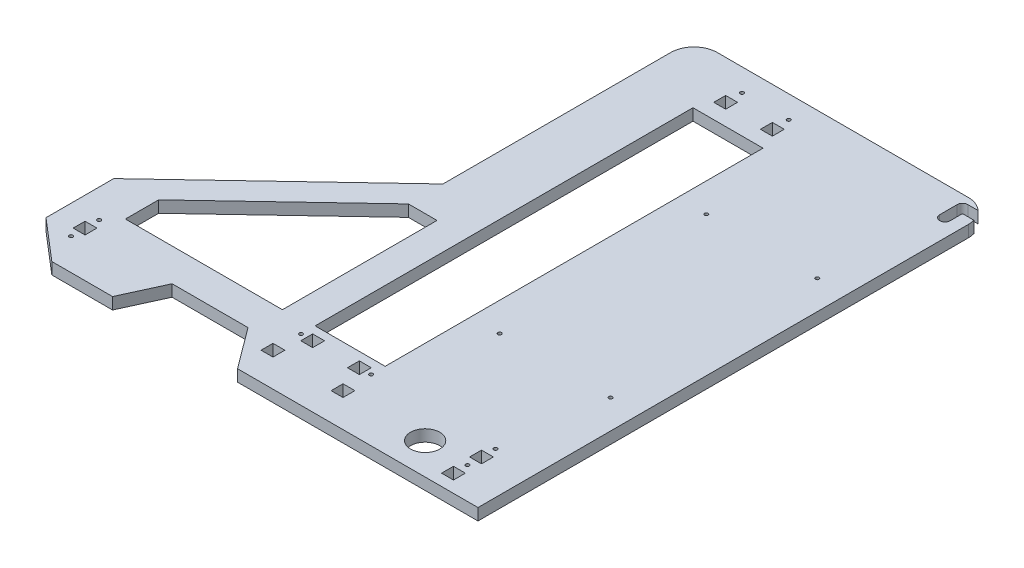
SolidWorks part; units mm, degrees
ref_plane "Front Plane" through (0, 0, 0) normal (0, 0, 1) x (1, 0, 0)
ref_plane "Top Plane" through (0, 0, 0) normal (0, 1, 0) x (1, 0, 0)
ref_plane "Right Plane" through (0, 0, 0) normal (1, 0, 0) x (0, 0, -1)
sketch "Sketch1" plane through (0, 0, 0) normal (0, 1, 0) x (1, 0, 0)
  line L0 (0, 0) -> (-235, 0)
  line L1 (-235, 0) -> (-235, -215)
  line L2 (-235, -215) -> (-380, -352)
  line L3 (-380, -352) -> (-380, -410)
  line L4 (-380, -410) -> (-345, -440)
  line L5 (-345, -440) -> (-293, -440)
  line L6 (-293, -440) -> (-277, -405)
  line L7 (-277, -405) -> (-212, -405)
  line L8 (-212, -405) -> (-185.9255, -440)
  line L9 (-185.9255, -440) -> (0, -440)
  line L10 (0, 0) -> (0, -440)
  line L12 (-293, -440) -> (-185.9255, -440) construction
  dimension "D3" = 235
  dimension "D5" = 58
  dimension "D13" = 190
  dimension "D7" = 35
  dimension "D2" = 126.686
  dimension "D11" = 65
  dimension "D15" = 52
  dimension "D12" = 30
  dimension "D10" = 35
  dimension "D14" = 16
  dimension "D6" = 380
  dimension "D4" = 440
extrude "Boss-Extrude1" add sketch "Sketch1" along normal blind 10
sketch "Sketch16" plane through (0, 10, 0) normal (0, 1, 0) x (1, 0, 0)
  line L0 (0, -440) -> (20, -440)
  line L1 (20, -440) -> (20, 0)
  line L2 (20, 0) -> (0, 0)
  line L3 (0, 0) -> (0, -440)
  dimension "D1" = 20
  dimension "D2" = 90
extrude "Boss-Extrude2" add sketch "Sketch16" against normal through all
sketch "Sketch2" plane through (0, 10, 0) normal (0, 1, 0) x (1, 0, 0)
  line L0 (-235, -215) -> (-235, -405) construction
  line L1 (-277, -405) -> (-212, -405) construction
  line L2 (-345, -440) -> (-345, -318.931) construction
  line L3 (-235, -215) -> (-380, -352) construction
  line L4 (-345, -348.5097) -> (-235, -244.5787)
  line L5 (-235, -244.5787) -> (-210.5, -244.5787)
  line L6 (-210.5, -244.5787) -> (-210.5, -377)
  line L7 (-210.5, -377) -> (-345, -377)
  line L8 (-345, -377) -> (-345, -348.5097)
  line L9 (0, -440) -> (0, 0) construction
  line L10 (-184.5, -375) -> (-124.5, -375)
  line L11 (-184.5, -375) -> (-184.5, -51.35)
  line L12 (-184.5, -51.35) -> (-124.5, -51.35)
  line L13 (-124.5, -375) -> (-124.5, -51.35)
  line L14 (-124.5, -387.1) -> (-184.5, -387.1) construction
  line L15 (-16, -440) -> (-16, 0) construction
  line L16 (20, 0) -> (-235, 0) construction
  line L17 (-355.55, -430.9571) -> (-355.55, -328.899) construction
  line L18 (-21.1, -430.1) -> (-10.9, -430.1)
  line L19 (-21.1, -430.1) -> (-21.1, -419.9)
  line L20 (-21.1, -419.9) -> (-10.9, -419.9)
  line L21 (-10.9, -430.1) -> (-10.9, -419.9)
  line L22 (-21.1, -430.1) -> (-10.9, -419.9) construction
  line L23 (-21.1, -419.9) -> (-10.9, -430.1) construction
  line L24 (-21.1, -406.1) -> (-10.9, -406.1)
  line L25 (-21.1, -406.1) -> (-21.1, -395.9)
  line L26 (-21.1, -395.9) -> (-10.9, -395.9)
  line L27 (-10.9, -406.1) -> (-10.9, -395.9)
  line L28 (-21.1, -406.1) -> (-10.9, -395.9) construction
  line L29 (-21.1, -395.9) -> (-10.9, -406.1) construction
  line L30 (-380, -410) -> (-345, -440) construction
  line L32 (-350.45, -395.9) -> (-360.65, -395.9)
  line L33 (-350.45, -395.9) -> (-350.45, -406.1)
  line L34 (-350.45, -406.1) -> (-360.65, -406.1)
  line L35 (-360.65, -395.9) -> (-360.65, -406.1)
  line L36 (-350.45, -395.9) -> (-360.65, -406.1) construction
  line L37 (-350.45, -406.1) -> (-360.65, -395.9) construction
  line L38 (-185.9255, -440) -> (20, -440) construction
  line L39 (-185.9255, -440) -> (20, -440) construction
  line L40 (-173.924, -33.35) -> (-113.924, -33.35) construction
  line L41 (-154.5, -51.35) -> (-154.5, -33.35) construction
  line L42 (-179.6, -28.25) -> (-169.4, -28.25)
  line L43 (-179.6, -28.25) -> (-179.6, -38.45)
  line L44 (-179.6, -38.45) -> (-169.4, -38.45)
  line L45 (-169.4, -28.25) -> (-169.4, -38.45)
  line L46 (-179.6, -28.25) -> (-169.4, -38.45) construction
  line L47 (-179.6, -38.45) -> (-169.4, -28.25) construction
  line L48 (-129.4, -38.45) -> (-139.6, -28.25) construction
  line L49 (-129.4, -28.25) -> (-139.6, -38.45) construction
  line L50 (-139.6, -28.25) -> (-139.6, -38.45)
  line L51 (-129.4, -38.45) -> (-139.6, -38.45)
  line L52 (-129.4, -28.25) -> (-129.4, -38.45)
  line L53 (-129.4, -28.25) -> (-139.6, -28.25)
  line L54 (-174.5, -33.35) -> (-174.5, -19.35) construction
  line L55 (-134.5, -33.35) -> (-134.5, -19.35) construction
  line L56 (-154.5, -375) -> (-154.5, -440) construction
  line L57 (-174.5, -387.1) -> (-134.5, -387.1) construction
  line L58 (-129.4, -392.2) -> (-139.6, -382) construction
  line L59 (-179.6, -382) -> (-169.4, -382)
  line L60 (-179.6, -382) -> (-179.6, -392.2)
  line L61 (-179.6, -392.2) -> (-169.4, -392.2)
  line L62 (-169.4, -382) -> (-169.4, -392.2)
  line L63 (-179.6, -382) -> (-169.4, -392.2) construction
  line L64 (-179.6, -392.2) -> (-169.4, -382) construction
  line L65 (-129.4, -382) -> (-139.6, -392.2) construction
  line L66 (-139.6, -382) -> (-139.6, -392.2)
  line L67 (-129.4, -392.2) -> (-139.6, -392.2)
  line L68 (-129.4, -382) -> (-129.4, -392.2)
  line L69 (-129.4, -382) -> (-139.6, -382)
  line L70 (-119.4, -416.2) -> (-129.6, -406) construction
  line L71 (-189.6, -406) -> (-179.4, -406)
  line L72 (-189.6, -406) -> (-189.6, -416.2)
  line L73 (-189.6, -416.2) -> (-179.4, -416.2)
  line L74 (-179.4, -406) -> (-179.4, -416.2)
  line L75 (-189.6, -406) -> (-179.4, -416.2) construction
  line L76 (-189.6, -416.2) -> (-179.4, -406) construction
  line L77 (-119.4, -406) -> (-129.6, -416.2) construction
  line L78 (-129.6, -406) -> (-129.6, -416.2)
  line L79 (-119.4, -416.2) -> (-129.6, -416.2)
  line L80 (-119.4, -406) -> (-119.4, -416.2)
  line L81 (-119.4, -406) -> (-129.6, -406)
  line L82 (-360.65, -395.9) -> (-10.9, -395.9) construction
  circle A0 centre (-16, -413) radius 1.55
  circle A1 centre (-16, -389) radius 1.55
  circle A2 centre (-355.55, -413) radius 1.55
  circle A3 centre (-355.55, -389) radius 1.55
  circle A4 centre (-174.5, -19.35) radius 1.55
  circle A5 centre (-134.5, -19.35) radius 1.55
  circle A6 centre (-124.5, -387.1) radius 1.55
  circle A7 centre (-184.5, -387.1) radius 1.55
  point P25 (-16, -425)
  point P30 (-16, -401)
  point P44 (-355.55, -401)
  point P61 (-174.5, -33.35)
  point P72 (-134.5, -33.35)
  point P85 (-174.5, -387.1)
  point P94 (-134.5, -387.1)
  point P95 (-184.5, -411.1)
  point P104 (-124.5, -411.1)
  point P105 (-154.5, -387.1)
  dimension "D13" = 3.1
  dimension "D14" = 3.1
  dimension "D23" = 3.1
  dimension "D24" = 3.1
  dimension "D31" = 3.1
  dimension "D37" = 3.1
  dimension "D1" = 21.5
  dimension "D2" = 28
  dimension "D3" = 24.5
  dimension "D4" = 60
  dimension "D7" = 26
  dimension "D8" = 10.2
  dimension "D9" = 10.2
  dimension "D10" = 10.2
  dimension "D11" = 10.2
  dimension "D12" = 24
  dimension "D15" = 24
  dimension "D19" = 10.2
  dimension "D20" = 10.2
  dimension "D26" = 12
  dimension "D27" = 10.2
  dimension "D28" = 10.2
  dimension "D33" = 10.2
  dimension "D38" = 10.2
  dimension "D39" = 10.2
  dimension "D41" = 24
  dimension "D34" = 30
  dimension "D36" = 12.1
  dimension "D30" = 18
  dimension "D29" = 40
  dimension "D17" = 15
  dimension "D32" = 14
  dimension "D35" = 20
  dimension "D16" = 12
  dimension "D21" = 90
  dimension "D25" = 24
  dimension "D5" = 353.75
  dimension "D22" = 349.75
  dimension "D40" = 30
  dimension "D6" = 65
  dimension "D42" = 0
  dimension "D43" = 0
  dimension "D18" = 16
extrude "Cut-Extrude1" cut sketch "Sketch2" against normal through all
fillet "Fillet1" radius 20 2 edges at (-235, 5, 0) (20, 5, 0)
sketch "Sketch11" plane through (0, 10, 0) normal (0, 1, 0) x (1, 0, 0)
  line L0 (-124.5, -213.175) -> (20, -213.175) construction
  line L1 (20, -440) -> (20, -20) construction
  line L3 (-52.25, -213.175) -> (-52.25, -440) construction
  line L6 (-124.5, -375) -> (-124.5, -51.35) construction
  line L8 (-185.9255, -440) -> (20, -440) construction
  circle A0 centre (-52.25, -413) radius 12.5
  circle A1 centre (-16, -413) radius 1.55 construction
  dimension "D1" = 25
  dimension "D2" = 0
  dimension "D3" = 0
extrude "WiringHole" cut sketch "Sketch11" against normal through all
sketch "Sketch9" plane through (0, 10, 0) normal (0, 1, 0) x (1, 0, 0)
  line L0 (-52.25, -400.5) -> (-52.25, 0) construction
  line L1 (0, 0) -> (-215, 0) construction
  line L2 (-124.5, -213.175) -> (20, -213.175) construction
  line L3 (-124.5, -375) -> (-124.5, -51.35) construction
  line L4 (-4.75, -124.675) -> (-4.75, -301.675) construction
  line L6 (-99.75, -124.675) -> (-4.75, -124.675) construction
  line L7 (-4.75, -301.675) -> (-99.75, -301.675) construction
  line L8 (-99.75, -301.675) -> (-99.75, -124.675) construction
  line L9 (20, -440) -> (20, -20) construction
  circle A0 centre (-52.25, -413) radius 12.5 construction
  circle A1 centre (-99.75, -124.675) radius 1.55
  circle A2 centre (-4.75, -124.675) radius 1.55
  circle A3 centre (-4.75, -301.675) radius 1.55
  circle A4 centre (-99.75, -301.675) radius 1.55
  dimension "D3" = 3.1
  dimension "D4" = 3.1
  dimension "D1" = 95
  dimension "D2" = 177
  dimension "D5" = 47.5
extrude "MountingHoles-PSU" cut sketch "Sketch9" against normal through all
sketch "Sketch10" [suppressed] plane through (0, 10, 0) normal (0, 1, 0) x (1, 0, 0)
  line L0 (-124.5, -213.175) -> (20, -213.175) construction
  line L1 (20, -440) -> (20, -20) construction
  line L2 (-64.75, -228.175) -> (-39.75, -228.175) construction
  line L3 (-52.25, -213.175) -> (-52.25, 0) construction
  line L7 (-124.5, -375) -> (-124.5, -51.35) construction
  line L8 (-64.75, -278.175) -> (-39.75, -278.175)
  line L9 (-64.75, -278.175) -> (-64.75, -178.175)
  line L10 (-64.75, -178.175) -> (-39.75, -178.175)
  line L11 (-39.75, -278.175) -> (-39.75, -178.175)
  line L12 (-64.75, -278.175) -> (-39.75, -178.175) construction
  line L13 (-64.75, -178.175) -> (-39.75, -278.175) construction
  line L15 (0, 0) -> (-215, 0) construction
  line L17 (-52.25, -213.175) -> (-52.25, -440) construction
  line L18 (-185.9255, -440) -> (20, -440) construction
  line L19 (-64.75, -213.175) -> (-39.75, -213.175) construction
  line L20 (-52.25, -278.175) -> (-52.25, -178.175) construction
  dimension "D1" = 25
  dimension "D2" = 100
  dimension "D3" = 0
  dimension "D4" = 0
  dimension "D5" = 0
  dimension "D6" = 15
extrude "WiringSlot" [suppressed] cut sketch "Sketch10" against normal through all
sketch "CenterLines" [suppressed] plane through (0, 10, 0) normal (0, 1, 0) x (1, 0, 0)
  line L0 (-52.25, -278.175) -> (-52.25, -178.175) construction
  line L1 (-64.75, -278.175) -> (-39.75, -278.175) construction
  line L2 (-39.75, -178.175) -> (-64.75, -178.175) construction
  line L3 (-64.75, -228.175) -> (-39.75, -228.175) construction
  line L4 (-64.75, -178.175) -> (-64.75, -278.175) construction
  line L5 (-39.75, -278.175) -> (-39.75, -178.175) construction
ref_plane "Plane1" [suppressed] through (-52.25, 0, 0) normal (1, 0, 0) x (0, 0, -1)
sketch "Sketch6" [suppressed] plane through (0, 10, 0) normal (0, 1, 0) x (1, 0, 0)
  line L0 (-52.25, -278.175) -> (-52.25, -178.175) construction
  line L1 (-76.35, -237.025) -> (-28.15, -237.025) construction
  line L2 (-28.15, -192.575) -> (-28.15, -275.075) construction
  line L3 (-64.75, -278.175) -> (-39.75, -278.175) construction
  line L4 (-64.75, -245.875) -> (-39.75, -245.875) construction
  line L5 (-39.75, -178.175) -> (-64.75, -178.175) construction
  line L6 (-28.15, -192.575) -> (-28.15, -199.575) construction
  line L7 (-26.6, -192.575) -> (-26.6, -199.575)
  line L8 (-29.7, -192.575) -> (-29.7, -199.575)
  line L9 (-64.75, -228.175) -> (-39.75, -228.175) construction
  line L10 (-64.75, -178.175) -> (-64.75, -278.175) construction
  line L11 (-39.75, -278.175) -> (-39.75, -178.175) construction
  line L12 (-28.15, -282.075) -> (-28.15, -275.075) construction
  line L13 (-29.7, -282.075) -> (-29.7, -275.075)
  line L14 (-76.35, -274.475) -> (-76.35, -199.575) construction
  line L15 (-28.15, -282.075) -> (-28.15, -199.575) construction
  line L16 (-26.6, -282.075) -> (-26.6, -275.075)
  arc A2 (-26.6, -192.575) -> (-29.7, -192.575) centre (-28.15, -192.575) ccw
  arc A3 (-29.7, -199.575) -> (-26.6, -199.575) centre (-28.15, -199.575) ccw
  circle A4 centre (-76.35, -274.475) radius 1.55
  circle A6 centre (-76.35, -199.575) radius 1.55
  arc A8 (-29.7, -282.075) -> (-26.6, -282.075) centre (-28.15, -282.075) ccw
  arc A9 (-26.6, -275.075) -> (-29.7, -275.075) centre (-28.15, -275.075) ccw
  point P20 (-28.15, -196.075)
  point P25 (-28.15, -278.575)
  dimension "D8" = 3.1
  dimension "D12" = 3.1
  dimension "D4" = 1.55
  dimension "D5" = 1.55
  dimension "D11" = 82.5
  dimension "D14" = 74.9
  dimension "D2" = 24.1
  dimension "D3" = 48.2
  dimension "D6" = 8.85
  dimension "D9" = 7
  dimension "D10" = 7
extrude "MountingHoles-RAMPS" [suppressed] cut sketch "Sketch6" against normal through all
mirror "Mirror1" [suppressed] about plane through (-52.25, 0, 0) normal (1, 0, 0)
sketch "Sketch5" [suppressed] plane through (0, 10, 0) normal (0, 1, 0) x (1, 0, 0)
  line L0 (-39.75, -228.175) -> (-64.75, -228.175) construction
  line L3 (-39.75, -278.175) -> (-39.75, -178.175) construction
  line L5 (-64.75, -178.175) -> (-64.75, -278.175) construction
  line L7 (-31.25, -127.675) -> (-73.25, -127.675) construction
  line L8 (-31.25, -328.675) -> (-73.25, -328.675) construction
  line L9 (-52.25, -228.175) -> (-52.25, -127.675) construction
  line L10 (-52.25, -228.175) -> (-52.25, -328.675) construction
  circle A0 centre (-73.25, -127.675) radius 1.55
  circle A1 centre (-31.25, -127.675) radius 1.55
  circle A2 centre (-31.25, -328.675) radius 1.55
  circle A3 centre (-73.25, -328.675) radius 1.55
  point P17 (-52.25, -127.675)
  point P22 (-52.25, -328.675)
  dimension "D2" = 3.1
  dimension "D5" = 3.1
  dimension "D6" = 3.1
  dimension "D7" = 3.1
  dimension "D3" = 201
  dimension "D4" = 100.5
  dimension "D8" = 21
  dimension "D9" = 21
  dimension "D10" = 100.5
extrude "MountingHoles-Melzi" [suppressed] cut sketch "Sketch5" against normal through all
sketch "Sketch13" [suppressed] plane through (0, 0, 0) normal (0, -1, 0) x (-1, 0, 0)
  line L0 (64.75, -213.175) -> (124.5, -213.175) construction
  line L1 (124.5, -375) -> (124.5, -51.35) construction
  line L2 (101.46, -262.69) -> (101.46, -163.66) construction
  line L3 (52.25, -278.175) -> (52.25, -178.175) construction
  line L4 (64.75, -178.175) -> (64.75, -278.175) construction
  line L6 (101.46, -262.69) -> (3.56, -262.69) construction
  circle A0 centre (101.46, -163.66) radius 1.55
  circle A1 centre (101.46, -262.69) radius 1.55
  circle A2 centre (8.62, -170.14) radius 1.55
  circle A3 centre (3.56, -262.69) radius 1.55
  point P11 (101.46, -213.175)
  dimension "D8" = 3.1
  dimension "D6" = 3.1
  dimension "D1" = 3.1
  dimension "D2" = 49.515
  dimension "D3" = 49.21
  dimension "D4" = 6.48
  dimension "D5" = 92.84
  dimension "D7" = 97.9
extrude "Mountingholes-Smoothieboard" [suppressed] cut sketch "Sketch13" against normal through all
mirror "Flipped" [suppressed] about plane through (-52.25, 0, 0) normal (1, 0, 0)
sketch "Sketch21" [suppressed] plane through (0, 10, 0) normal (0, 1, 0) x (1, 0, 0)
  line L0 (-52.25, -178.175) -> (-52.25, 0) construction
  line L1 (-39.75, -178.175) -> (-64.75, -178.175) construction
  line L2 (0, 0) -> (-215, 0) construction
  line L3 (-52.25, -62.675) -> (-23.3697, -62.675) construction
  circle A0 centre (-27.75, -33.675) radius 1.55
  circle A1 centre (-76.75, -33.675) radius 1.55
  circle A2 centre (-76.75, -91.675) radius 1.55
  circle A3 centre (-27.75, -91.675) radius 1.55
  circle A4 centre (-31.25, -127.675) radius 1.55 construction
  dimension "D1" = 3.1
  dimension "D2" = 24.5
  dimension "D3" = 29
  dimension "D4" = 65
extrude "Pi" [suppressed] cut sketch "Sketch21" against normal through all
sketch "Sketch17" plane through (0, 10, 0) normal (0, 1, 0) x (1, 0, 0)
  line L0 (0, 0) -> (20, 0) construction
  line L1 (20, -23.6361) -> (20, 0) construction
  line L2 (20, -440) -> (20, -20) construction
  line L3 (20, -10) -> (5, -10) construction
  line L4 (20, -14.5) -> (5, -14.5)
  line L5 (20, -5.5) -> (5, -5.5)
  arc A0 (20, -14.5) -> (20, -5.5) centre (20, -10) ccw
  arc A1 (5, -5.5) -> (5, -14.5) centre (5, -10) ccw
  point P8 (12.5, -10)
  dimension "D1" = 9
  dimension "D2" = 15
  dimension "D3" = 10
extrude "Cut-Extrude3" cut sketch "Sketch17" against normal through all
sketch "Sketch18" plane through (0, 10, 0) normal (0, 1, 0) x (1, 0, 0)
  line L0 (5, -5.5) -> (5, -14.5) construction
  line L1 (0.5, -10) -> (5, -10) construction
  line L2 (5, -10) -> (5, -25) construction
  line L3 (9.5, -10) -> (9.5, -25)
  line L4 (0.5, -10) -> (0.5, -25)
  arc A0 (5, -5.5) -> (5, -14.5) centre (5, -10) ccw construction
  arc A1 (9.5, -10) -> (0.5, -10) centre (5, -10) ccw
  arc A2 (0.5, -25) -> (9.5, -25) centre (5, -25) ccw
  point P10 (5, -17.5)
  dimension "D1" = 9
  dimension "D2" = 0
  dimension "D3" = 15
extrude "Cut-Extrude4" cut sketch "Sketch18" against normal through all
sketch "Sketch19" plane through (0, 10, 0) normal (0, 1, 0) x (1, 0, 0)
  line L0 (-5, -25) -> (15, -25) construction
  line L1 (5, -25) -> (5, -5.5) construction
  circle A0 centre (15, -25) radius 1.55
  arc A1 (5, -5.5) -> (0.5, -10) centre (5, -10) ccw construction
  circle A2 centre (-5, -25) radius 1.55
  dimension "D2" = 3.1
extrude "Cut-Extrude5" [suppressed] cut sketch "Sketch19" against normal through all
equation "\"Y-ROD-SPACING\"=75"
equation "\"Y-BED-OFFSET\"=2"
equation "\"Y-BED-ROD-INSET\"=3.5"
equation "\"T-SLOT-NUT-FILLET-RADIUS\"=0.25"
equation "\"T-SLOT-SCREW-SHAFT-RADIUS\"=1.75"
equation "\"T-SLOT-SCREW-SHAFT-CUTOUT-LENGTH\"=10.5"
equation "\"T-SLOT-NUT-DEPTH\"=4.2"
equation "\"T-SLOT-NUT-WIDTH\"=3"
equation "\"T-SLOT-NUT-END-DISTANCE\"=8"
equation "\"ACRYLIC-TAB-CUTOUT-SIZE\"=\"ACRYLIC-THICKNESS\"+\"ACRYLIC-TAB-TOLERANCE\"*2"
equation "\"ACRYLIC-TAB-WIDTH\"=\"ACRYLIC-THICKNESS\""
equation "\"ACRYLIC-M3-HOLE\"=3.1"
equation "\"SMOOTHROD-CAP-SCREW-DISTANCE\"=20"
equation "\"FRAME-WIDTH-INNER\"=370"
equation "\"D24@Sketch2\"=\"ACRYLIC-M3-HOLE\""
equation "\"D23@Sketch2\"=\"ACRYLIC-M3-HOLE\""
equation "\"D19@Sketch2\"=\"ACRYLIC-THICKNESS\"+\"ACRYLIC-TAB-TOLERANCE\"*2"
equation "\"D20@Sketch2\"=\"ACRYLIC-TAB-WIDTH\"+\"ACRYLIC-TAB-TOLERANCE\"*2"
equation "\"D37@Sketch2\"=\"ACRYLIC-M3-HOLE\""
equation "\"D33@Sketch2\"=\"ACRYLIC-TAB-CUTOUT-SIZE\""
equation "\"D38@Sketch2\"=\"ACRYLIC-TAB-CUTOUT-SIZE\""
equation "\"D39@Sketch2\"=\"ACRYLIC-TAB-CUTOUT-SIZE\""
equation "\"D13@Sketch2\"=\"ACRYLIC-M3-HOLE\""
equation "\"D14@Sketch2\"=\"ACRYLIC-M3-HOLE\""
equation "\"D8@Sketch2\"=\"ACRYLIC-TAB-CUTOUT-SIZE\""
equation "\"D9@Sketch2\"=\"ACRYLIC-TAB-CUTOUT-SIZE\""
equation "\"D10@Sketch2\"=\"ACRYLIC-TAB-CUTOUT-SIZE\""
equation "\"D11@Sketch2\"=\"ACRYLIC-TAB-CUTOUT-SIZE\""
equation "\"D31@Sketch2\"=\"ACRYLIC-M3-HOLE\""
equation "\"D27@Sketch2\"=\"ACRYLIC-THICKNESS\"+\"ACRYLIC-TAB-TOLERANCE\"*2"
equation "\"D28@Sketch2\"=\"ACRYLIC-TAB-WIDTH\"+\"ACRYLIC-TAB-TOLERANCE\"*2"
equation "\"NEMA17-HOLE-SPACING\"=31"
equation "\"NEMA17-CENTRAL-CUTOUT\"=22.5"
equation "\"Z-BRACKET-REACH\"=55"
equation "\"TOP-BRACKET-SPACING\"=40"
equation "\"D29@Sketch2\"=\"TOP-BRACKET-SPACING\""
equation "\"ACRYLIC-THICKNESS\"=10"
equation "\"SMOOTHROD-Z-LENGTH\"=350"
equation "\"D5@Sketch2\"=\"SMOOTHROD-Z-LENGTH\"-\"SMOOTHROD-TIGHTENING-HEADROOM\"+4"
equation "\"SMOOTHROD-X-LENGTH\"=350"
equation "\"SMOOTHROD-Y-LENGTH\"=350"
equation "\"D22@Sketch2\"=\"SMOOTHROD-Y-LENGTH\"-\"SMOOTHROD-TIGHTENING-HEADROOM\""
equation "\"SMOOTHROD-TIGHTENING-HEADROOM\"=.25"
equation "\"X-ROD-SPACING\"=45"
equation "\"Z-ROD-SPACING\"=17.5"
equation "\"LEADSCREW-Z-LENGTH\"=300"
equation "\"SCREW-HEAD-RADIUS\"=6"
equation "\"PRINTED-X-SMOOTHROD-DIAMETER\"=8.2"
equation "\"PRINTED-X-SMOOTHROD-CUTOUT\"=10"
equation "\"PRINTED-X-BASE-HEIGHT\"=10"
equation "\"PRINTED-LM8UU-CUTOUT-SIZE\"=15.25"
equation "\"PRINTED-LM8UU-CUTOUT-LENGTH\"=24.5"
equation "\"PRINTED-X-IDLER-HEIGHT\"=16"
equation "\"PSU-MOUNTING-WIDTH\"=95"
equation "\"PSU-MOUNTING-HEIGHT\"=177"
equation "\"D1@Sketch9\"=\"PSU-MOUNTING-WIDTH\""
equation "\"D3@Sketch9\"=\"ACRYLIC-M3-HOLE\""
equation "\"D1@Boss-Extrude1\"=\"ACRYLIC-THICKNESS\""
equation "\"D6@Sketch1\"=\"SMOOTHROD-Y-LENGTH\"+30"
equation "\"D4@Sketch9\"=\"ACRYLIC-M3-HOLE\""
equation "\"D2@Sketch9\"=\"PSU-MOUNTING-HEIGHT\""
equation "\"D5@Sketch9\"=\"PSU-MOUNTING-WIDTH\"/2"
equation "\"D4@Sketch1\"=\"SMOOTHROD-Z-LENGTH\"+90"
equation "\"D8@Sketch6\"=\"ACRYLIC-M3-HOLE\""
equation "\"D12@Sketch6\"=\"ACRYLIC-M3-HOLE\""
equation "\"D2@Sketch5\"=\"ACRYLIC-M3-HOLE\""
equation "\"D5@Sketch5\"=\"ACRYLIC-M3-HOLE\""
equation "\"D6@Sketch5\"=\"ACRYLIC-M3-HOLE\""
equation "\"D7@Sketch5\"=\"ACRYLIC-M3-HOLE\""
equation "\"D1@Sketch13\"=\"ACRYLIC-M3-HOLE\""
equation "\"D6@Sketch13\"=\"ACRYLIC-M3-HOLE\""
equation "\"D8@Sketch13\"=\"ACRYLIC-M3-HOLE\""
equation "\"D4@Sketch6\"=\"ACRYLIC-M3-HOLE\"/2"
equation "\"D5@Sketch6\"=\"ACRYLIC-M3-HOLE\"/2"
equation "\"Y-BED-SCREW-SPACING\"=209"
equation "\"Y-BED-SCREW-CUTOUT-SLOT-HEIGHT\"=2"
equation "\"ACRYLIC-THICKNESS2\"=4.5"
equation "\"ACRYLIC-TAB-TOLERANCE\"=.1"
equation "\"Z-ROD-INSET\"=16"
equation "\"SCREW-LENGTH-FRAME\"=\"ACRYLIC-THICKNESS\" + 10"
equation "\"SCREW-LENGTH-MOTOR\"=\"ACRYLIC-THICKNESS\" + 5"
equation "\"SCREW-LENGTH-EXTRUDER\"=28"
equation "\"Y-BELT-TO-ROD-DISTANCE\"=20"
equation "\"SPOOL-HOLDER-ROD-SPACING\"=150"
equation "\"ACRYLIC-X-CARRIAGE-WIDTH\"=55"
equation "\"ACRYLIC-X-CARRIAGE-HEIGHT\"=75"
equation "\"ACRYLIC-X-CARRIAGE-LM8UU-CUTOUT-WIDTH\"=24.25"
equation "\"ACRYLIC-X-CARRIAGE-SCREW-SPACING-X\"=15"
equation "\"ACRYLIC-X-CARRIAGE-SCREW-SPACING-Y\"=33"
equation "\"ACRYLIC-X-CARRIAGE-CENTER-TAB-SPACING\"=14"
equation "\"ACRYLIC-X-CARRIAGE-EXTRUDER-OFFSET\"=26"
equation "\"ACRYLIC-X-CARRIAGE-EXTRUDER-ANGLE\"=90"
equation "\"ACRYLIC-X-CARRIAGE-EXTRUDER-SHELF-DEPTH\"=\"ACRYLIC-X-CARRIAGE-EXTRUDER-OFFSET\" + 28"
equation "\"ACRYLIC-X-CARRIAGE-EXTRUDER-BRACE-SPACING\"=23"
equation "\"ACRYLIC-X-CARRIAGE-EXTRUDER-BRACE-TAB-OFFSET\"=20"
equation "\"ACRYLIC-X-CARRIAGE-EXTRUDER-BRACE-HEIGHT\"=35"
equation "\"ACRYLIC-X-CARRIAGE-EXTRUDER-BRACE-SCREW-SPACING\"=22"
equation "\"D1@Sketch19\"=\"SMOOTHROD-CAP-SCREW-DISTANCE\"/2"
equation "\"D2@Sketch19\"=\"ACRYLIC-M3-HOLE\""
equation "\"D1@Sketch21\"=\"ACRYLIC-M3-HOLE\""
